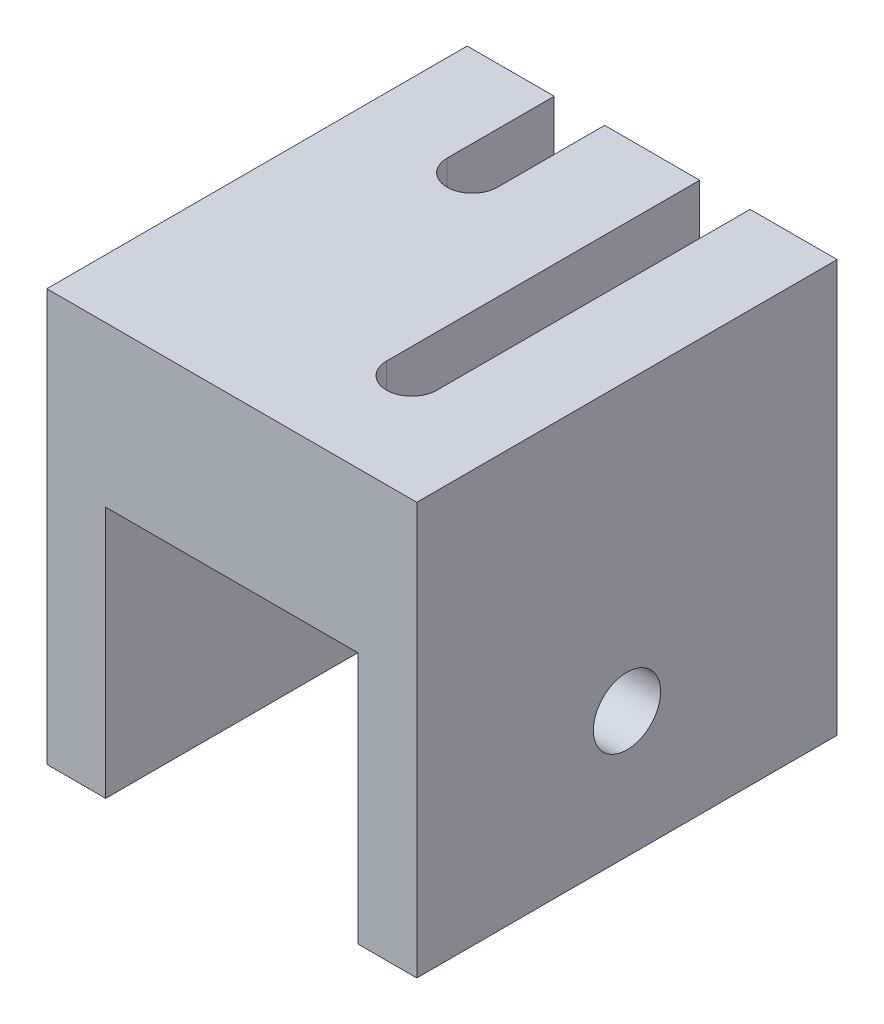
SolidWorks part; units mm, degrees
ref_plane "Front Plane" through (0, 0, 0) normal (0, 0, 1) x (1, 0, 0)
ref_plane "Top Plane" through (0, 0, 0) normal (0, 1, 0) x (1, 0, 0)
ref_plane "Right Plane" through (0, 0, 0) normal (1, 0, 0) x (0, 0, -1)
sketch "Sketch1" plane through (0, 0, 0) normal (0, 0, 1) x (1, 0, 0)
  line L0 (-22, -15) -> (-22, 22)
  line L5 (-15, 15) -> (15, -15) construction
  line L6 (-15, -15) -> (15, 15) construction
  line L11 (-22, 22) -> (22, 22)
  line L12 (22, -15) -> (22, 22)
  line L13 (-15, -15) -> (15, -15)
  line L14 (-15, -15) -> (-15, 15)
  line L15 (-15, 15) -> (15, 15)
  line L16 (15, -15) -> (15, 15)
  line L17 (-15, -15) -> (15, 15) construction
  line L18 (-15, 15) -> (15, -15) construction
  line L19 (-22, -15) -> (-15, -15)
  line L20 (15, -15) -> (22, -15)
  line L22 (-15, -15) -> (-22, -15)
  line L23 (-15, -15) -> (-15, 22)
  line L24 (-15, 22) -> (-22, 22)
  line L25 (-22, -15) -> (-22, 22)
  line L26 (-15, 22) -> (22, 22)
  line L27 (-15, 22) -> (-15, 15)
  line L28 (-15, 15) -> (22, 15)
  line L29 (22, 22) -> (22, 15)
  line L30 (22, -15) -> (15, -15)
  line L31 (22, -15) -> (22, 15)
  line L32 (22, 15) -> (15, 15)
  line L33 (15, -15) -> (15, 15)
  point P0 (0, 0)
  point P6 (0, 29.5014)
  point P11 (0, 0)
  dimension "D1" = 30
  dimension "D2" = 7
  dimension "D3" = 30
extrude "Boss-Extrude1" add sketch "Sketch1" along normal blind 50 contours L15 L28 L12 L11 L23 | L28 L16 L20 L12 | L23 L22 L25 L24 region at (3.5, 18.5, 0) region at (18.5, 0, 0)
sketch "Sketch3" plane through (0, 22, 0) normal (0, 1, 0) x (1, 0, 0)
  line L0 (0, 0) -> (0, -50) construction
  line L2 (-22, 0) -> (22, 0) construction
  line L5 (-22, -50) -> (22, -50) construction
  line L6 (0, -25) -> (-22, -25) construction
  line L7 (-22, -50) -> (-22, 0) construction
  line L8 (0, -25) -> (-8.6502, -12.7455) construction
  line L9 (0, -25) -> (8.6502, -37.2545) construction
  line L16 (-13.6502, -12.7455) -> (-13.6502, 0)
  line L17 (-3.6502, -12.7455) -> (-3.6502, 0)
  line L18 (3.6502, -37.2545) -> (3.6502, 0)
  line L19 (13.6502, -37.2545) -> (13.6502, 0)
  circle A2 centre (-8.6502, -12.7455) radius 5
  circle A3 centre (8.6502, -37.2545) radius 5
  line M13 (22, 0) -> (-22, 0)
  line M14 (-22, 0) -> (-22, -50)
  line M15 (-22, -50) -> (22, -50)
  line M16 (22, -50) -> (22, 0)
  dimension "D1" = 10
  dimension "D2" = 10
extrude "Boss-Extrude2" add sketch "Sketch3" along normal blind 6 contours M16 | M14 | A3 L18 L17 A2 L16 L19 M13 M14 M15 M16 region at (-1.3075, 22, 27.8256)
sketch "Sketch4" plane through (0, 28, 0) normal (0, 1, 0) x (1, 0, 0)
  line L0 (5.6502, -37.2545) -> (5.6502, 0)
  line L1 (3.6502, 0) -> (13.6502, 0) construction
  line L2 (11.6502, -37.2545) -> (11.6502, 0)
  line L3 (-11.6502, -12.7455) -> (-11.6502, 0)
  line L4 (-13.6502, 0) -> (-3.6502, 0) construction
  line L5 (-5.6502, -12.7455) -> (-5.6502, 0)
  line L6 (-11.6502, 0) -> (-13.6502, 0)
  line L7 (-13.6502, 0) -> (-13.6502, -12.7455)
  line L8 (-3.6502, -12.7455) -> (-3.6502, 0)
  line L9 (-3.6502, -12.7455) -> (-3.6502, 0) construction
  line L10 (-3.6502, 0) -> (-5.6502, 0)
  line L11 (13.6502, -37.2545) -> (13.6502, 0)
  line L12 (13.6502, 0) -> (11.6502, 0)
  line L13 (3.6502, -37.2545) -> (3.6502, 0)
  line L14 (3.6502, 0) -> (5.6502, 0)
  circle A0 centre (8.6502, -37.2545) radius 3
  circle A1 centre (-8.6502, -12.7455) radius 3
  arc A2 (-13.6502, -12.7455) -> (-3.6502, -12.7455) centre (-8.6502, -12.7455) ccw
  arc A3 (-13.6502, -12.7455) -> (-3.6502, -12.7455) centre (-8.6502, -12.7455) ccw construction
  arc A4 (13.6502, -37.2545) -> (3.6502, -37.2545) centre (8.6502, -37.2545) cw
  arc A5 (3.6502, -37.2545) -> (13.6502, -37.2545) centre (8.6502, -37.2545) ccw construction
  arc M1 (13.6502, -37.2545) -> (3.6502, -37.2545) centre (8.6502, -37.2545) cw
  line M2 (3.6502, -37.2545) -> (3.6502, 0)
  line M3 (3.6502, 0) -> (-3.6502, 0)
  line M4 (-3.6502, 0) -> (-3.6502, -12.7455)
  arc M5 (-3.6502, -12.7455) -> (-13.6502, -12.7455) centre (-8.6502, -12.7455) cw
  line M6 (-13.6502, -12.7455) -> (-13.6502, 0)
  line M7 (-13.6502, 0) -> (-22, 0)
  line M8 (-22, 0) -> (-22, -50)
  line M9 (-22, -50) -> (22, -50)
  line M10 (22, -50) -> (22, 0)
  line M11 (22, 0) -> (13.6502, 0)
  line M12 (13.6502, 0) -> (13.6502, -37.2545)
  dimension "D1" = 6
  dimension "D2" = 6
extrude "Boss-Extrude4" add sketch "Sketch4" along normal blind 6 contours A0 L0 L14 L12 L2 M2 M1 M12 | A1 L3 L6 L10 L5 M6 M5 M4 | M12 M1 M2 M3 M4 M5 M6 M7 M8 M9 M10 M11 region at (8.6502, 28, 40.6887) region at (-1.3075, 28, 27.8256) region at (-3.8539, 28, 6.3727)
sketch "Sketch5" plane through (-22, 0, 0) normal (-1, 0, 0) x (0, 0, 1)
  line L0 (25, -15) -> (25, -4) construction
  line L1 (50, -15) -> (0, -15) construction
  line L2 (25, -4) -> (25, 4) construction
  line L3 (0, -4) -> (50, -4)
  line L4 (50, -15) -> (50, 34) construction
  line L5 (0, 4) -> (50, 4)
  line L6 (29, 0) -> (50, 0) construction
  circle A0 centre (25, 0) radius 4
  point P10 (25, -4)
  point P13 (25, 4)
  dimension "D1" = 11
  dimension "D2" = 8
extrude "Cut-Extrude1" cut sketch "Sketch5" against normal blind 59 contours A0 L5 region at (-22, 0, 25)
